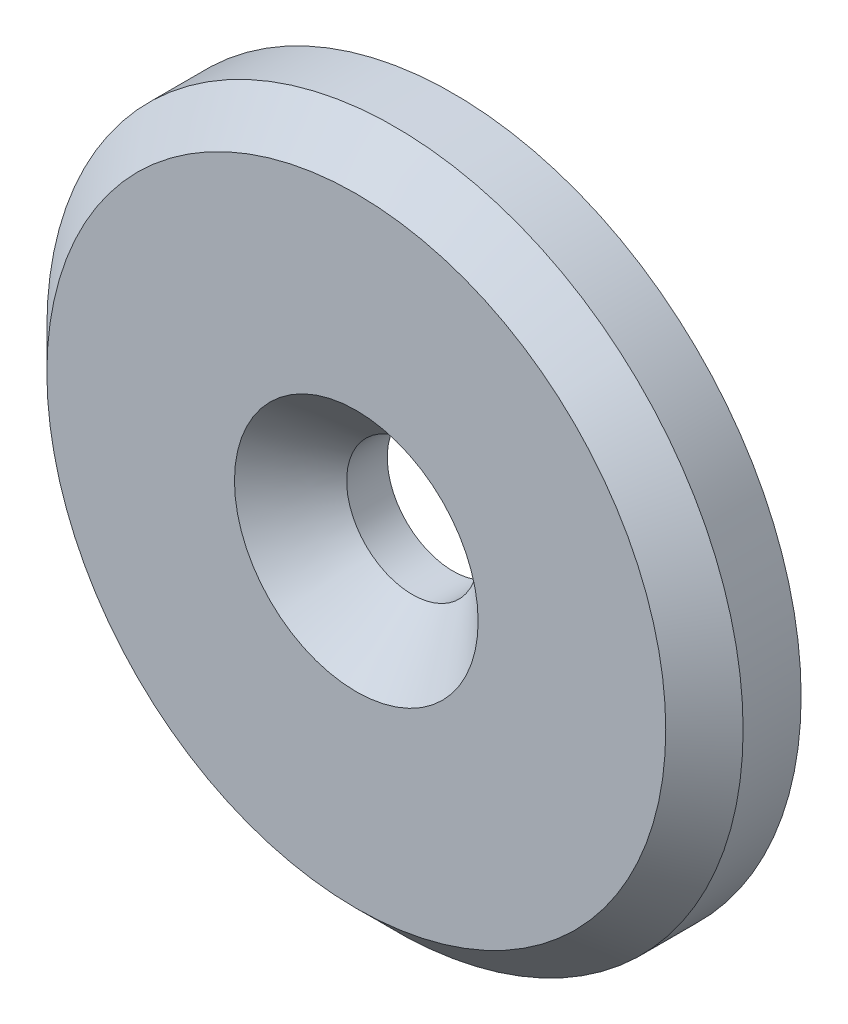
SolidWorks part; units mm, degrees
ref_plane "Спереди" through (0, 0, 0) normal (0, 0, 1) x (1, 0, 0)
ref_plane "Сверху" through (0, 0, 0) normal (0, 1, 0) x (1, 0, 0)
ref_plane "Справа" through (0, 0, 0) normal (1, 0, 0) x (0, 0, -1)
sketch "Эскиз1" plane through (0, 0, 0) normal (0, 0, 1) x (1, 0, 0)
  circle A0 centre (0, 0) radius 9
  circle A1 centre (0, 0) radius 5 construction
  dimension "D1" = 4
extrude "Бобышка-Вытянуть1" add sketch "Эскиз1" along normal blind 2.5
chamfer "Фаска1" distance 1 angle 45 1 edges at (9, 0, 2.5)
hole_wizard "Зенковка для винта с полупотайной головкой M31" positions "Эскиз2" profile "Эскиз4" countersink size "M3" standard "ISO" end condition through all
sketch "Эскиз2" plane through (0, 0, 2.5) normal (0, 0, 1) x (1, 0, 0)
  point P0 (0, 0)
sketch "Эскиз4" plane through (0, 0, 2.5) normal (1, 0, 0) x (0, -1, 0)
  line L0 (0, 0) -> (0, 2.5)
  line L1 (0, 2.5) -> (1.7, 2.5)
  line L2 (1.7, 2.5) -> (1.7, 1.45)
  line L3 (1.7, 1.45) -> (3.15, 0)
  line L5 (3.15, 0) -> (0, 0)
  line L6 (-1.7, 1.45) -> (-3.15, 0) construction
  line L11 (0, -6.35) -> (0, 107.95) construction
  dimension "Диаметр сквозного отверстия" = 3.4
  dimension "Глубина сквозного отверстия" = 2.5
  dimension "Диаметр передней зенковки" = 6.3
  dimension "Угол передней зенковки" = 90
